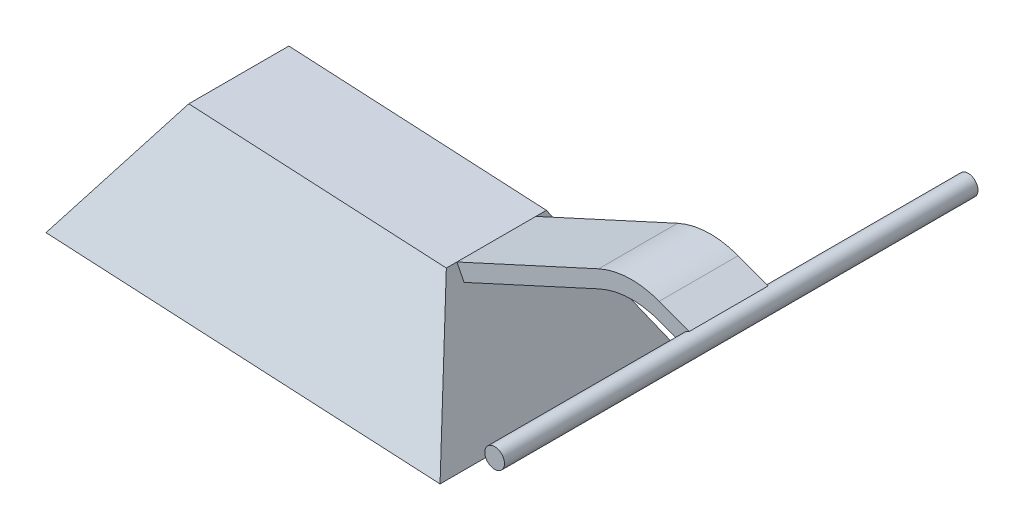
SolidWorks part; units mm, degrees
ref_plane "前视基准面" through (0, 0, 0) normal (0, 0, 1) x (1, 0, 0)
ref_plane "上视基准面" through (0, 0, 0) normal (0, 1, 0) x (1, 0, 0)
ref_plane "右视基准面" through (0, 0, 0) normal (1, 0, 0) x (0, 0, -1)
sketch "草图1" plane through (85.9411, -2.2504, 0) normal (-0.0523, -0.9986, 0) x (-0.9986, 0.0523, 0)
  line L0 (85.9411, 0) -> (89.6377, 0) construction
  line L1 (85.9411, 0) -> (85.9411, 60.0356) construction
  line L3 (60.9411, -15) -> (110.9411, -15)
  line L4 (60.9411, -15) -> (60.9411, 15)
  line L5 (60.9411, 15) -> (110.9411, 15)
  line L6 (110.9411, -15) -> (110.9411, 15)
  line L7 (60.9411, -15) -> (110.9411, 15) construction
  line L8 (60.9411, 15) -> (110.9411, -15) construction
  dimension "D1" = 50
  dimension "D2" = 30
extrude "凸台-拉伸1" add sketch "草图1" against normal blind 15 draft 30
sketch "草图2" plane through (0, 0, 0) normal (0, 0, 1) x (1, 0, 0)
  line L0 (47, 20) -> (47, 25.6367) construction
  line L1 (45.5, 20) -> (48.5, 20) construction
  circle A0 centre (47, 22.25) radius 1.25
  point P6 (0, 0)
  dimension "D1" = 2.5
  dimension "D2" = 1
extrude "凸台-拉伸2" add sketch "草图2" along normal mid plane 60 separate body
sketch "草图3" plane through (0, 0, 0) normal (0, 0, 1) x (1, 0, 0)
  line L0 (16.1099, 14.763) -> (39, 25.25)
  line L1 (39, 25.25) -> (47, 22.25)
  point P2 (19.9678, 12.882)
  point P3 (20.9087, 12.0218)
  point P6 (12.7378, 12.3915)
  point P7 (16.2792, 14.4011)
  dimension "D1" = 3
  dimension "D2" = 8
  dimension "D3" = 1
extrude "拉伸-薄壁1" add sketch "草图3" along normal mid plane 10 thin thin type mid plane wall 2
fillet "圆角1" radius 10 2 edges at (39.0384, 24.1676, 0) (38.9616, 26.3324, 0)
